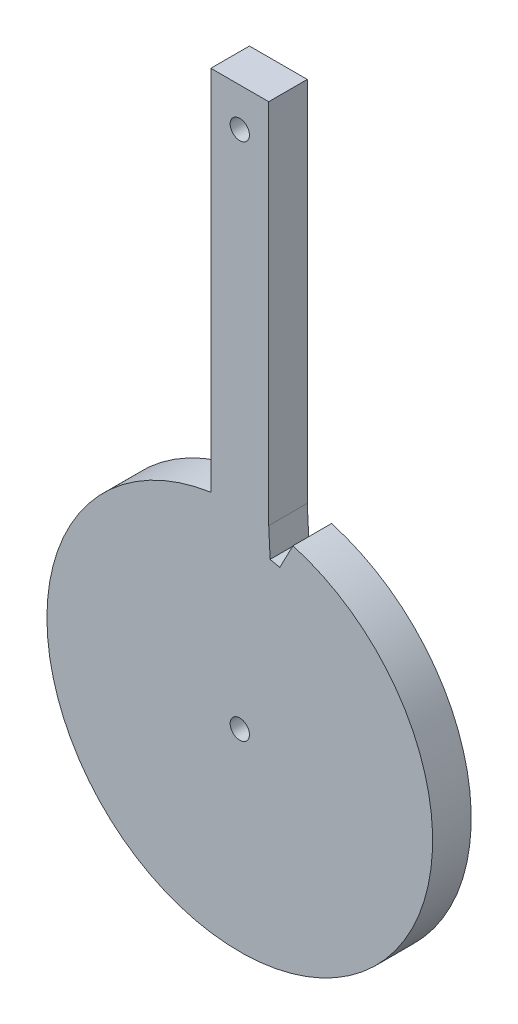
SolidWorks part; units mm, degrees
note: '?' marks a value the reader was unsure of.
material "Acrylic (Medium-high impact)"
ref_plane "Front Plane" through (0, 0, 0) normal (0, 0, 1) x (1, 0, 0)
ref_plane "Top Plane" through (0, 0, 0) normal (0, 1, 0) x (1, 0, 0)
ref_plane "Right Plane" through (0, 0, 0) normal (1, 0, 0) x (0, 0, -1)
sketch "Sketch2" plane through (0, 0, 0) normal (0, 0, 1) x (1, 0, 0)
  line L0 (7.5, 49.4343) -> (7.5, 144.62)
  line L1 (7.5, 144.62) -> (-7.5, 144.62)
  line L2 (-7.5, 144.62) -> (-7.5, 49.4343)
  line L3 (0, 0) -> (0, 144.62) construction
  arc A0 (-7.5, 49.4343) -> (7.5, 49.4343) centre (0, 0) ccw
  dimension "D1" = 50
  dimension "D2" = 15
  dimension "D3" = 15
  dimension "D4" = 144.62
base flange "Base-Flange1" sketch "Sketch2" thickness 10 reverse thickness direction no parameters "D1"=0.7366
sketch "Sketch7" plane through (0, 0, 0) normal (0, 0, 1) x (1, 0, 0)
  line L0 (7.5, 144.62) -> (-7.5, 144.62) construction
  line L1 (7.5, 49.4343) -> (7.5, 144.62) construction
  circle A0 centre (0, 134.62) radius 2.5
  circle A1 centre (0, 0) radius 2.5
  point P2 (0, 144.62)
  dimension "D1" = 5
  dimension "D2" = 10
  dimension "D3" = 7.5
extrude "Cut-Extrude1" cut sketch "Sketch7" against normal up to next normal cut yes
ref_axis "Axis1" through (0, 0, -10) along (0, 0, 1)?
sketch "Sketch8" plane through (0, 0, 0) normal (0, 0, 1) x (1, 0, 0)
  line L0 (0, 0) -> (10.668, 48.8487) construction
  line L1 (7.5, 49.4343) -> (7.8717, 42.0436)
  line L2 (0, 0) -> (7.5, 49.4343) construction
  line L3 (10.3727, 41.4974) -> (13.7917, 48.0603)
  line L4 (0, 0) -> (13.7917, 48.0603) construction
  line L5 (7.8717, 42.0436) -> (10.3727, 41.4974)
  line L7 (-7.5, 49.4343) -> (0, 0) construction
  arc A1 (-7.5, 49.4343) -> (7.5, 49.4343) centre (0, 0) ccw construction
  arc A2 (7.5, 49.4343) -> (13.7917, 48.0603) centre (0, 0) cw
  point P7 (7.5, 49.4343)
  dimension "D1" = 7.4
  dimension "D4" = 6.44
  dimension "D2" = 2.56
extrude "Cut-Extrude2" cut sketch "Sketch8" against normal up to next normal cut yes
sketch "Bend-Lines1" [suppressed] plane through (0, 0, 0) normal (0, 1, 0) x (1, 0, 0)
sketch "Bounding-Box1" [suppressed] plane through (0, 0, 0) normal (0, 1, 0) x (1, 0, 0)
sheet metal parameters "Sheet-Metal1" thickness 10 parameters "D1"=0.7366
flat pattern "Flat-Pattern1" [suppressed]
sketch "Bend-Lines2" plane through (0, 0, 0) normal (0, 1, 0) x (1, 0, 0)
sketch "Bounding-Box2" [suppressed] plane through (0, 0, 0) normal (0, 1, 0) x (1, 0, 0)
sheet metal parameters "Sheet-Metal2" thickness 10 parameters "D1"=0.7366
flat pattern "Flat-Pattern1"
sketch "Bend-Lines2" plane through (0, 0, 0) normal (0, 1, 0) x (1, 0, 0)
sketch3d "Bounding-Box2" [suppressed]
  line L0 (6.184, 148.8636, 0) -> (62.5663, -32.9462, 0) construction
  line L1 (-89.3286, 119.2436, 0) -> (-32.9462, -62.5663, 0) construction
  line L2 (6.184, 148.8636, 0) -> (-89.3286, 119.2436, 0) construction
  line L3 (62.5663, -32.9462, 0) -> (-32.9462, -62.5663, 0) construction
sheet metal parameters "Sheet-Metal3" thickness 10 parameters "D1"=0.7366
flat pattern "Flat-Pattern1"
sketch "Bend-Lines2" plane through (0, 0, 0) normal (0, 1, 0) x (1, 0, 0)
sketch3d "Bounding-Box2" [suppressed]
  line L0 (6.184, 148.8636, 0) -> (62.5663, -32.9462, 0) construction
  line L1 (-89.3286, 119.2436, 0) -> (-32.9462, -62.5663, 0) construction
  line L2 (6.184, 148.8636, 0) -> (-89.3286, 119.2436, 0) construction
  line L3 (62.5663, -32.9462, 0) -> (-32.9462, -62.5663, 0) construction
